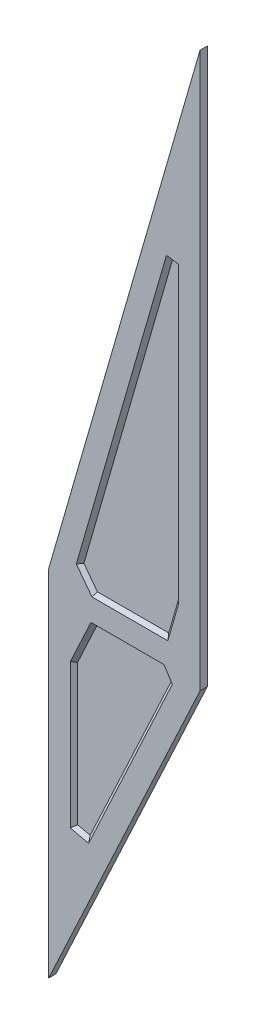
SolidWorks part; units mm, degrees
ref_plane "Plan de face" through (0, 0, 0) normal (0, 0, 1) x (1, 0, 0)
ref_plane "Plan de dessus" through (0, 0, 0) normal (0, 1, 0) x (1, 0, 0)
ref_plane "Plan de droite" through (0, 0, 0) normal (1, 0, 0) x (0, 0, -1)
sketch "Esquisse1" plane through (0, 0, 0) normal (0, 0, 1) x (1, 0, 0)
  line L0 (210, 769.9989) -> (0, 42.1417)
  line L1 (0, 42.1417) -> (0, 0)
  line L2 (0, 0) -> (210, 727.8571) construction
  line L3 (210, 727.8571) -> (210, 769.9989)
  line L4 (210, 769.9989) -> (209.579, 771.1189)
  line L5 (210, 727.8571) -> (210, 0)
  line L6 (210, 0) -> (0, 0) construction
  line L7 (0, 0) -> (0, -450)
  line L8 (0, -450) -> (210, 0)
  line L9 (210, 0) -> (210.5402, 0.5304)
  dimension "D1" = 210
  dimension "D2" = 769.9989
  dimension "D3" = 11.6821
  dimension "D4" = 450
extrude "Boss.-Extru.1" add sketch "Esquisse1" along normal blind 10 contours L7 L8 L5 L3 L0 L1 region at (112.7052, 112.1437, 0)
sketch "Esquisse2" plane through (0, 0, 10) normal (0, 0, 1) x (1, 0, 0)
  line L0 (60, 37.9004) -> (165.3026, 37.9004)
  line L1 (180, 88.8413) -> (180, 497.7984)
  line L2 (58.6117, 6.6555) -> (30, -54.6554)
  line L3 (160, 6.6555) -> (58.6117, 6.6555)
  line L4 (180, 497.7984) -> (163.3673, 500.1498)
  line L5 (55.3731, -260.4021) -> (30, -254.7731)
  line L6 (30, -54.6554) -> (30, -254.7731)
  line L7 (0, -450) -> (210, 0) construction
  line L8 (30, 37.9004) -> (30, -314.7731)
  line L9 (30, -314.7731) -> (180, 6.6555)
  line L10 (180, 6.6555) -> (180, 557.7984)
  line L11 (180, 557.7984) -> (30, 37.9004)
  line L12 (30, 37.9004) -> (30, -314.7731) construction
  line L13 (55.3731, -260.4021) -> (171.5423, -11.4682)
  line L14 (180, 6.6555) -> (180, 557.7984) construction
  line L15 (163.3673, 500.1498) -> (38.3163, 66.7247)
  line L16 (180, 88.8413) -> (165.3026, 37.9004)
  line L17 (210, 769.9989) -> (0, 42.1417) construction
  line L18 (38.3163, 66.7247) -> (60, 37.9004)
  line L19 (171.5423, -11.4682) -> (160, 6.6555)
  dimension "D2" = 160
  dimension "D3" = 140
  dimension "D1" = 30
extrude "Enlèv. mat.-Extru.1" cut sketch "Esquisse2" against normal blind 5
chamfer "Chanfrein1" distance 5 angle 45 12 edges at (165.7711, -2.4064, 5) (113.4577, -135.9351, 5) (42.6866, -257.5876, 5) (30, -154.7142, 5) (44.3059, -23.9999, 5) (109.3059, 6.6555, 5) (171.6837, 498.9741, 5) (180, 293.3199, 5) (172.6513, 63.3709, 5) (112.6513, 37.9004, 5) (49.1582, 52.3126, 5) (100.8418, 283.4373, 5)
